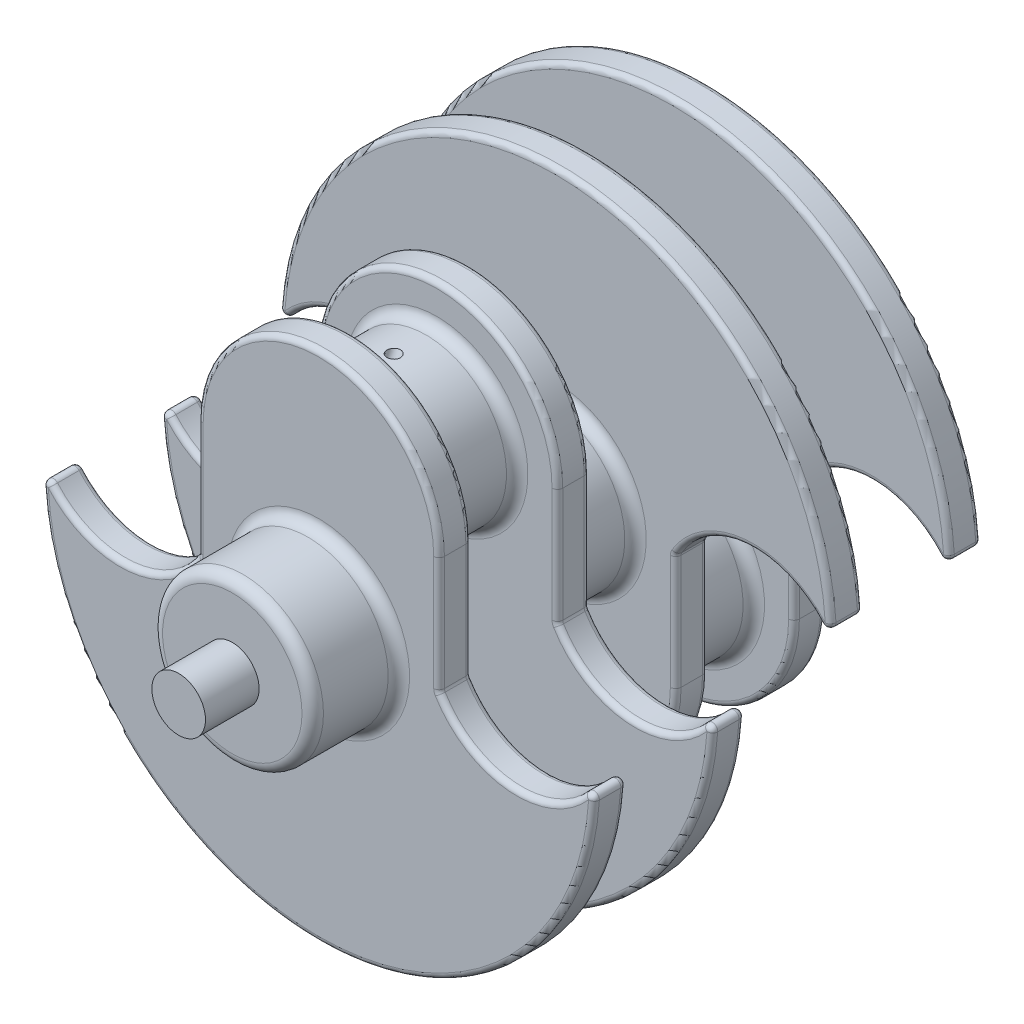
SolidWorks part; units mm, degrees
material "AISI 4340 Steel, normalized"
ref_plane "Front Plane" through (0, 0, 0) normal (0, 0, 1) x (1, 0, 0)
ref_plane "Top Plane" through (0, 0, 0) normal (0, 1, 0) x (1, 0, 0)
ref_plane "Right Plane" through (0, 0, 0) normal (1, 0, 0) x (0, 0, -1)
sketch "Sketch1" plane through (0, 0, 0) normal (0, 0, 1) x (1, 0, 0)
  circle A0 centre (0, 0) radius 30
  dimension "D1" = 30
extrude "Boss-Extrude1" add sketch "Sketch1" along normal blind 32.13
sketch "Sketch8" plane through (0, 0, 0) normal (0, 0, -1) x (-1, 0, 0)
  line L0 (-45, 43.2) -> (-45, 0)
  line L1 (45, 43.2) -> (45, 0)
  line L2 (-45, 0) -> (-89.1072, 0) construction
  arc A0 (45, 43.2) -> (-45, 43.2) centre (0, 43.2) ccw
  arc A5 (-103, 0) -> (103, 0) centre (0, 0) ccw
  arc A6 (-45, 0) -> (-103, 0) centre (-74, 16.8638) cw
  arc A7 (45, 0) -> (103, 0) centre (74, 16.8638) ccw
  dimension "D1" = 45
  dimension "D2" = 103
  dimension "D3" = 43.2
  dimension "D4" = 0
  dimension "D5" = 180
  dimension "D6" = 0
extrude "Boss-Extrude5" add sketch "Sketch8" along normal blind 12
sketch "Sketch2" plane through (0, 0, 32.13) normal (0, 0, 1) x (1, 0, 0)
  circle A0 centre (0, 0) radius 10
  dimension "D1" = 10
extrude "Boss-Extrude2" add sketch "Sketch2" along normal blind 20
sketch "Sketch9" plane through (0, 0, -12) normal (0, 0, -1) x (-1, 0, 0)
  circle A0 centre (0, 43.2) radius 30
  dimension "D2" = 30
  dimension "D1" = 43.2
extrude "Boss-Extrude6" add sketch "Sketch9" along normal blind 32.13
ref_plane "Plane4" through (0, 0, -88.26) normal (0, 0, -1) x (-1, 0, 0)
sketch "Sketch10" plane through (0, 0, -44.13) normal (0, 0, -1) x (-1, 0, 0)
  line L0 (-45, -43.2) -> (-45, 0)
  line L1 (45, -43.2) -> (45, 0)
  line L2 (45, 0) -> (85.967, 0) construction
  arc A0 (-45, -43.2) -> (45, -43.2) centre (0, -43.2) ccw
  arc A1 (-45, 0) -> (-103, 0) centre (-74, -16.8638) ccw
  arc A2 (45, 0) -> (103, 0) centre (74, -16.8638) cw
  arc A3 (-103, 0) -> (103, 0) centre (0, 0) cw
  dimension "D1" = 45
  dimension "D4" = 0
  dimension "D5" = 180
  dimension "D6" = 0
  dimension "D3" = 103
  dimension "D2" = 43.2
extrude "Boss-Extrude7" add sketch "Sketch10" along normal blind 12 from surface starting at plane "Plane4"
ref_plane "Plane3" through (0, 0, -132.39) normal (0, 0, -1) x (-1, 0, 0)
sketch "Sketch12" plane through (0, 0, -132.39) normal (0, 0, -1) x (-1, 0, 0)
  line L2 (45, -43.2) -> (45, 0)
  line L3 (45, -43.2) -> (45, 0)
  line L4 (-45, 0) -> (-45, -43.2)
  line L5 (-45, 0) -> (-45, -43.2)
  arc A12 (-45, -43.2) -> (45, -43.2) centre (0, -43.2) ccw
  arc A13 (103, 0) -> (45, 0) centre (74, -16.8638) ccw
  arc A14 (103, 0) -> (-103, 0) centre (0, 0) ccw
  arc A15 (-45, 0) -> (-103, 0) centre (-74, -16.8638) ccw
  arc A16 (-45, -43.2) -> (45, -43.2) centre (0, -43.2) ccw
  arc A17 (103, 0) -> (45, 0) centre (74, -16.8638) ccw
  arc A18 (103, 0) -> (-103, 0) centre (0, 0) ccw
  arc A19 (-45, 0) -> (-103, 0) centre (-74, -16.8638) ccw
  dimension "D1" = 0
extrude "Boss-Extrude8" add sketch "Sketch12" along normal blind 12
sketch "Sketch14" plane through (0, 0, -100.26) normal (0, 0, -1) x (-1, 0, 0)
  circle A0 centre (0, -43.2) radius 30
  dimension "D2" = 30
  dimension "D1" = 43.2
extrude "Boss-Extrude9" add sketch "Sketch14" along normal up to next
sketch "Sketch15" plane through (0, 0, -144.39) normal (0, 0, -1) x (-1, 0, 0)
  circle A1 centre (0, 0) radius 30
  circle A2 centre (0, 0) radius 30
  dimension "D1" = 0
extrude "Boss-Extrude10" add sketch "Sketch15" along normal blind 32.13
sketch "Sketch16" plane through (0, 0, -176.52) normal (0, 0, -1) x (-1, 0, 0)
  circle A1 centre (0, 0) radius 10
  circle A2 centre (0, 0) radius 10
  dimension "D1" = 0
extrude "Boss-Extrude11" add sketch "Sketch16" along normal blind 20
sketch "Sketch18" plane through (0, 0, -44.13) normal (0, 0, -1) x (-1, 0, 0)
  line L2 (-45, 43.2) -> (-45, 0)
  line L3 (-45, 43.2) -> (-45, 0)
  line L4 (45, 0) -> (45, 43.2)
  line L5 (45, 0) -> (45, 43.2)
  arc A4 (45, 43.2) -> (-45, 43.2) centre (0, 43.2) ccw
  arc A5 (-103, 0) -> (-45, 0) centre (-74, 16.8638) ccw
  arc A6 (-103, 0) -> (103, 0) centre (0, 0) ccw
  arc A7 (45, 0) -> (103, 0) centre (74, 16.8638) ccw
  arc A8 (45, 43.2) -> (-45, 43.2) centre (0, 43.2) ccw
  arc A9 (-103, 0) -> (-45, 0) centre (-74, 16.8638) ccw
  arc A10 (-103, 0) -> (103, 0) centre (0, 0) ccw
  arc A11 (45, 0) -> (103, 0) centre (74, 16.8638) ccw
  dimension "D1" = 0
extrude "Boss-Extrude12" add sketch "Sketch18" along normal blind 12
sketch "Sketch19" plane through (0, 0, -56.13) normal (0, 0, -1) x (-1, 0, 0)
  circle A1 centre (0, 0) radius 30
  circle A2 centre (0, 0) radius 30
  dimension "D1" = 0
extrude "Boss-Extrude13" add sketch "Sketch19" along normal up to next
fillet "Fillet1" radius 2 32 edges at (0, -103, -44.13) (-74, -16.683, -44.13) (-45, 21.6, -44.13) (45, 21.6, -44.13) (74, -16.683, -44.13) (0, -103, -56.13) (-74, -16.683, -56.13) (-45, 21.6, -56.13) (0, 88.2, -56.13) (45, 21.6, -56.13) (74, -16.683, -56.13) (103, 0, -50.13) (45, 0, -50.13) (-45, 0, -50.13) (-103, 0, -50.13) (0, 88.2, -44.13) (45, 21.6, 0) (74, -16.683, 0) (0, -103, 0) (-74, -16.683, 0) (-45, 21.6, 0) (0, 88.2, -12) (45, 21.6, -12) (74, -16.683, -12) (0, -103, -12) (-74, -16.683, -12) (-45, 21.6, -12) (-45, 0, -6) (-103, 0, -6) (103, 0, -6) (45, 0, -6) (0, 88.2, 0)
fillet "Fillet2" radius 2 16 edges at (0, 103, -132.39) (74, 16.683, -132.39) (45, -21.6, -132.39) (0, -88.2, -132.39) (-45, -21.6, -132.39) (-74, 16.683, -132.39) (74, 16.683, -144.39) (45, -21.6, -144.39) (0, -88.2, -144.39) (-45, -21.6, -144.39) (-74, 16.683, -144.39) (-103, 0, -138.39) (-45, 0, -138.39) (45, 0, -138.39) (103, 0, -138.39) (0, 103, -144.39)
fillet "Fillet3" radius 2 16 edges at (45, -21.6, -88.26) (74, 16.683, -88.26) (0, 103, -88.26) (-74, 16.683, -88.26) (-45, -21.6, -88.26) (0, -88.2, -88.26) (45, -21.6, -100.26) (74, 16.683, -100.26) (-74, 16.683, -100.26) (-45, -21.6, -100.26) (0, -88.2, -100.26) (45, 0, -94.26) (103, 0, -94.26) (-103, 0, -94.26) (-45, 0, -94.26) (0, 103, -100.26)
fillet "Fillet5" radius 4 2 edges at (30, 0, 32.13) (30, 0, 0)
fillet "Fillet6" radius 4 2 edges at (-30, 0, -144.39) (-30, 0, -176.52)
ref_plane "Plane5" through (0, 31.75, 0) normal (0, 1, 0) x (1, 0, 0)
sketch "Sketch20" plane through (0, 0, 0) normal (1, 0, 0) x (0, 0, -1)
  line L1 (100.26, -73.2) -> (100.26, -13.2)
  line L2 (100.26, -73.2) -> (100.26, -13.2)
  dimension "D1" = 0
ref_plane "Plane6" through (0, -73.2, 0) normal (0, 1, 0) x (1, 0, 0)
sketch "Sketch21" plane through (0, 31.75, 0) normal (0, 1, 0) x (1, 0, 0)
  line L2 (-30, 172.52) -> (30, 172.52) construction
  line L3 (-30, 172.52) -> (-30, 148.39) construction
  line L4 (-30, 148.39) -> (30, 148.39) construction
  line L5 (30, 172.52) -> (30, 148.39) construction
  circle A0 centre (0, 160.455) radius 2.5
  point P10 (0, 172.52)
  point P11 (30, 160.455)
  dimension "D1" = 5
sketch "Sketch27" plane through (0, 0, 0) normal (0, 0, 1) x (1, 0, 0)
  line L0 (0, 73.2) -> (0, -30) construction
  circle A1 centre (0, 43.2) radius 30
  circle A2 centre (0, 43.2) radius 30 construction
  circle A3 centre (0, 0) radius 30
  circle A4 centre (0, 0) radius 30 construction
  dimension "D1" = 0
  dimension "D2" = 0
ref_plane "Plane8" through (0, 73.2, 0) normal (0, -1, 0) x (-1, 0, 0)
ref_plane "Plane9" through (0, -30, 0) normal (0, -1, 0) x (-1, 0, 0)
sketch "Sketch28" plane through (0, -30, 0) normal (0, -1, 0) x (-1, 0, 0)
  line L1 (-30, -4) -> (30, -4) construction
  line L2 (-30, -4) -> (-30, -28.13) construction
  line L3 (-30, -28.13) -> (30, -28.13) construction
  line L4 (30, -4) -> (30, -28.13) construction
  line L5 (-30, -4) -> (30, -28.13) construction
  line L6 (-30, -28.13) -> (30, -4) construction
  circle A0 centre (0, -16.065) radius 2.5
  point P4 (0, -16.065)
  dimension "D1" = 5
sketch "Sketch29" plane through (0, 73.2, 0) normal (0, -1, 0) x (-1, 0, 0)
  line L1 (30, 44.13) -> (-30, 44.13) construction
  line L2 (30, 44.13) -> (30, 12) construction
  line L3 (30, 12) -> (-30, 12) construction
  line L4 (-30, 44.13) -> (-30, 12) construction
  line L5 (30, 44.13) -> (-30, 12) construction
  line L6 (30, 12) -> (-30, 44.13) construction
  circle A0 centre (0, 28.065) radius 2.5
  point P4 (0, 28.065)
sketch "Sketch31" plane through (0, 0, 0) normal (1, 0, 0) x (0, 0, -1)
  line L0 (28.065, 73.2) -> (-16.065, -30) construction
  line L1 (44.13, 86.2) -> (44.13, 43.2) construction
  line L2 (12, 43.2) -> (12, 86.2) construction
  line L3 (44.13, 86.2) -> (44.13, 43.2) construction
  line L4 (12, 43.2) -> (12, 86.2) construction
  dimension "D1" = 16.065
ref_plane "Plane10" through (0, 73.2, -28.065) normal (0, -0.9195, 0.3932) x (-1, 0, 0)
ref_plane "Plane11" through (0, -30, 16.065) normal (0, -0.9195, 0.3932) x (-1, 0, 0)
combine bodies "Combine1" operation type add bodies to combine 119 109 117
fillet "Fillet7" radius 4 6 edges at (-30, 43.2, -44.13) (-30, 43.2, -12) (-30, 0, -56.13) (-30, 0, -88.26) (-30, -43.2, -132.39) (-30, -43.2, -100.26)
sketch "Sketch39" plane through (0, -73.2, 0) normal (0, 1, 0) x (1, 0, 0)
  line L1 (30, 128.39) -> (-30, 128.39) construction
  line L2 (30, 128.39) -> (30, 104.26) construction
  line L3 (30, 104.26) -> (-30, 104.26) construction
  line L4 (-30, 128.39) -> (-30, 104.26) construction
  line L5 (30, 128.39) -> (-30, 104.26) construction
  line L6 (30, 104.26) -> (-30, 128.39) construction
  point P4 (0, 116.325)
sketch "Sketch40" plane through (0, 0, 0) normal (1, 0, 0) x (0, 0, -1)
  line L0 (160.455, 31.75) -> (116.325, -73.2) construction
  line L1 (172.52, 31.75) -> (148.39, 31.75) construction
  line L3 (132.39, -43.2) -> (132.39, -86.2) construction
  dimension "D1" = 16.065
ref_plane "Plane12" through (0, 31.75, -160.455) normal (0, -0.9218, 0.3876) x (-1, 0, 0)
ref_plane "Plane13" through (0, -73.2, -116.325) normal (0, -0.9218, 0.3876) x (-1, 0, 0)
sketch "Sketch47" plane through (0, 73.2, -28.065) normal (0, -0.9195, 0.3932) x (-1, 0, 0)
  ellipse E0 centre (0, 0) end of major axis (2.5, 0) minor radius 2.2987 construction
  ellipse E1 centre (0, 0) end of major axis (2.5, 0) minor radius 2.2987
sketch "Sketch48" plane through (0, -30, 16.065) normal (0, -0.9195, 0.3932) x (-1, 0, 0)
  ellipse E0 centre (0, 0) end of major axis (2.5, 0) minor radius 2.2987 construction
  ellipse E1 centre (0, 0) end of major axis (2.5, 0) minor radius 2.2987
extrude "Cut-Extrude2" cut sketch "Sketch48" against normal through all
sketch "Sketch49" plane through (0, -73.2, -116.325) normal (0, -0.9218, 0.3876) x (-1, 0, 0)
  circle A0 centre (0, 0) radius 2.5
  dimension "D1" = 5
extrude "Cut-Extrude3" cut sketch "Sketch49" against normal through all
sketch "Sketch50" plane through (0, 31.75, -160.455) normal (0, -0.9218, 0.3876) x (-1, 0, 0)
  circle A0 centre (0, 0) radius 2.5 construction
  circle A1 centre (0, 0) radius 2.5
extrude "Cut-Extrude4" cut sketch "Sketch50" along normal through all
sketch "Sketch51" plane through (0, 0, 0) normal (1, 0, 0) x (0, 0, -1)
  line L0 (28.065, 73.2) -> (116.325, -73.2) construction
ref_plane "Plane14" through (0, 73.2, -28.065) normal (0, -0.8564, -0.5163) x (-1, 0, 0)
sketch "Sketch52" plane through (0, 73.2, -28.065) normal (0, -0.9195, 0.3932) x (-1, 0, 0)
  ellipse E0 centre (0, 0) end of major axis (2.5, 0) minor radius 2.2987 construction
  ellipse E1 centre (0, 0) end of major axis (2.5, 0) minor radius 2.2987
extrude "Cut-Extrude5" cut sketch "Sketch52" along normal through all and the other way through all
equation "\"CRR\"= 43.2mm'Crank Radius"
equation "\"D1@Sketch9\"=\"CRR\""
equation "\"D1@Sketch14\"=\"CRR\""
equation "\"JR\"= 30mm'Journal Radius"
equation "\"D1@Sketch1\"=\"JR\""
equation "\"D2@Sketch9\"=\"JR\""
equation "\"D2@Sketch14\"=\"JR\""
equation "\"LT\"= 12mm'Lobe Thickness"
equation "\"D1@Boss-Extrude5\"=\"LT\""
equation "\"D1@Boss-Extrude7\"=\"LT\""
equation "\"D1@Boss-Extrude8\"=\"LT\""
equation "\"D1@Boss-Extrude12\"=\"LT\""
equation "\"D3@Sketch8\"=\"CRR\""
equation "\"D2@Sketch10\"=\"CRR\""
equation "\"JL\"= 24.13 + 2 * ( \"JF\" )'Journal Length"
equation "\"D1@Boss-Extrude1\"=\"JL\""
equation "\"D1@Boss-Extrude6\"=\"JL\""
equation "\"D1@Boss-Extrude10\"=\"JL\""
equation "\"LHD\"= 5mm'Lubrication Hole Diameter"
equation "\"D1@Sketch29\"=\"LHD\""
equation "\"JF\"= 4mm'Internal Journal Fillets"
equation "\"D1@Fillet7\"=\"JF\""
equation "\"D1@Fillet6\"=\"JF\""
equation "\"LR\"= 45mm'Lobe radius"
equation "\"CWR\"= 103mm'Counterweight Radius"
equation "\"D1@Sketch8\"=\"LR\""
equation "\"D2@Sketch8\"=\"CWR\""
equation "\"D3@Sketch10\"=\"CWR\""
equation "\"D1@Sketch10\"=\"LR\""
equation "\"CWA\"= 3.14159rad'Counterweight Arc"
equation "\"CWS\"= 0rad'Counterweight Slope"
equation "\"CWH\"= 0mm'Counterweight Offset"
equation "\"D4@Sketch8\"=\"CWH\""
equation "\"D5@Sketch8\"=\"CWA\""
equation "\"D6@Sketch8\"=\"CWS\""
equation "\"D4@Sketch10\"=\"CWH\""
equation "\"D5@Sketch10\"=\"CWA\""
equation "\"D6@Sketch10\"=\"CWS\""
